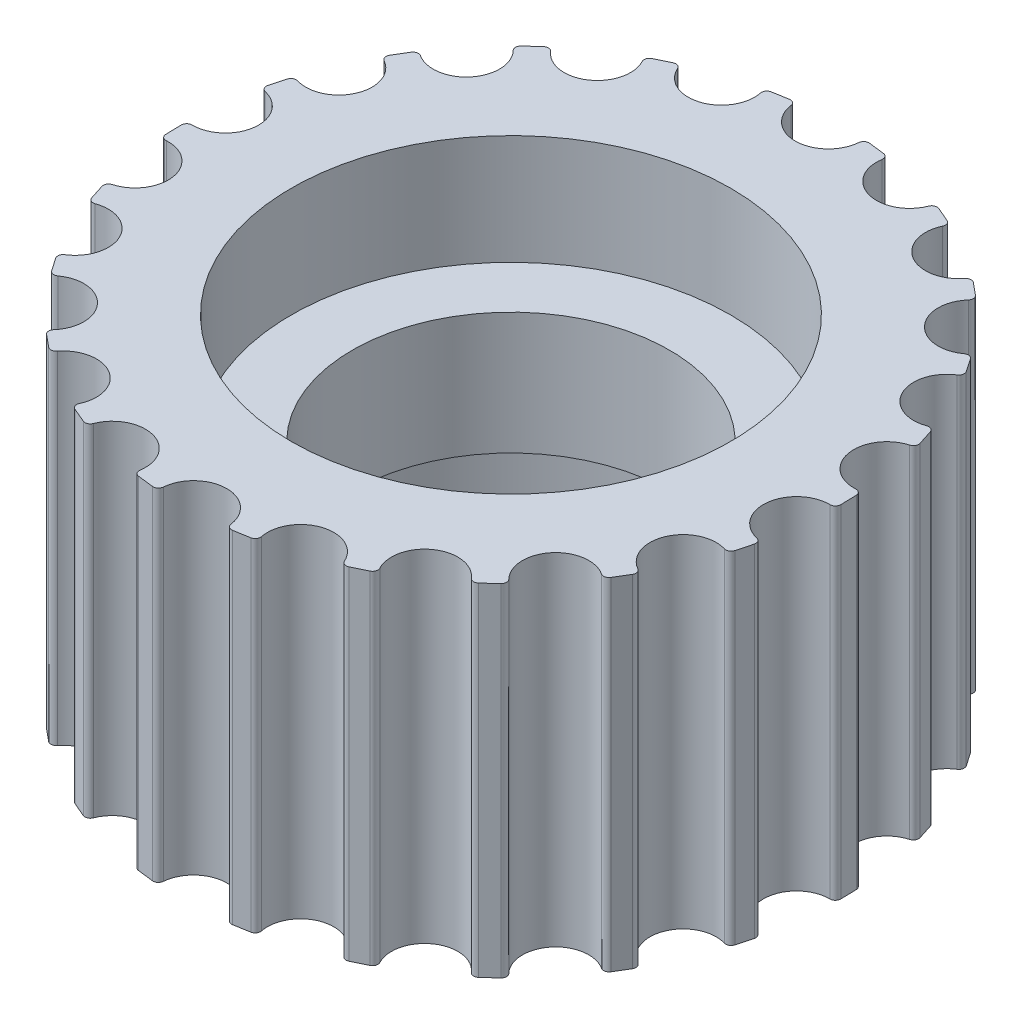
SolidWorks part; units mm, degrees
ref_plane "Front Plane" through (0, 0, 0) normal (0, 0, 1) x (1, 0, 0)
ref_plane "Top Plane" through (0, 0, 0) normal (0, 1, 0) x (1, 0, 0)
ref_plane "Right Plane" through (0, 0, 0) normal (1, 0, 0) x (0, 0, -1)
sketch "Sketch2" plane through (0, 0, 0) normal (0, 1, 0) x (1, 0, 0)
  line L0 (-1.2929, 6.625) -> (-0.973, 6.6795)
  line L1 (0.6256, 6.7209) -> (0.9479, 6.6831)
  line L2 (2.4934, 6.2725) -> (2.792, 6.1454)
  line L3 (4.1593, 5.3159) -> (4.4099, 5.1099)
  line L4 (5.4881, 3.9288) -> (5.6706, 3.6605)
  line L5 (6.3724, 2.2235) -> (6.4718, 1.9146)
  line L6 (6.7404, 0.3382) -> (6.7488, 0.0138)
  line L7 (6.5623, -1.5745) -> (6.479, -1.8881)
  line L8 (5.8526, -3.3595) -> (5.6843, -3.6369)
  line L9 (4.6687, -4.8722) -> (4.429, -5.091)
  line L10 (3.1066, -5.9901) -> (2.815, -6.1325)
  line L11 (1.2928, -6.6227) -> (0.9729, -6.6772)
  line L12 (-0.6257, -6.7186) -> (-0.948, -6.6808)
  line L13 (-2.4936, -6.2702) -> (-2.7921, -6.143)
  line L14 (-4.1594, -5.3136) -> (-4.4101, -5.1075)
  line L15 (-5.4883, -3.9265) -> (-5.6707, -3.6582)
  line L16 (-6.3725, -2.2212) -> (-6.472, -1.9123)
  line L17 (-6.7405, -0.3359) -> (-6.7489, -0.0115)
  line L18 (-6.5624, 1.5768) -> (-6.4791, 1.8904)
  line L19 (-5.8527, 3.3618) -> (-5.6844, 3.6392)
  line L20 (-4.6688, 4.8745) -> (-4.4292, 5.0933)
  line L21 (-3.1067, 5.9925) -> (-2.8151, 6.1349)
  circle A0 centre (0, 0) radius 4.5
  circle A1 centre (0, 0) radius 6 construction
  circle A2 centre (0, 0) radius 6.75 construction
  circle A3 centre (0, 0) radius 7.03 construction
  arc A4 (-0.973, 6.6795) -> (-0.8456, 6.5859) centre (-0.9546, 6.5711) cw
  arc A5 (-0.8456, 6.5859) -> (0.5058, 6.6207) centre (-0.1718, 6.6778) ccw
  arc A6 (0.5058, 6.6207) -> (0.6256, 6.7209) centre (0.6154, 6.6114) cw
  arc A7 (0.9479, 6.6831) -> (1.0438, 6.5574) centre (0.9351, 6.5738) cw
  arc A8 (1.0438, 6.5574) -> (2.3502, 6.21) centre (1.7162, 6.4557) ccw
  arc A9 (2.3502, 6.21) -> (2.4934, 6.2725) centre (2.4528, 6.1703) cw
  arc A10 (2.792, 6.1454) -> (2.8487, 5.9977) centre (2.7489, 6.0442) cw
  arc A11 (2.8487, 5.9977) -> (4.0043, 5.2964) centre (3.4651, 5.7107) ccw
  arc A12 (4.0043, 5.2964) -> (4.1593, 5.3159) centre (4.0915, 5.2293) cw
  arc A13 (4.4099, 5.1099) -> (4.4227, 4.9523) centre (4.3401, 5.0249) cw
  arc A14 (4.4227, 4.9523) -> (5.3339, 3.9537) centre (4.9333, 4.5032) ccw
  arc A15 (5.3339, 3.9537) -> (5.4881, 3.9288) centre (5.3987, 3.8648) cw
  arc A16 (5.6706, 3.6605) -> (5.6384, 3.5057) centre (5.5796, 3.5986) cw
  arc A17 (5.6384, 3.5057) -> (6.2314, 2.2909) centre (6.0019, 2.9309) ccw
  arc A18 (6.2314, 2.2909) -> (6.3724, 2.2235) centre (6.2685, 2.1873) cw
  arc A19 (6.4718, 1.9146) -> (6.3974, 1.7752) centre (6.3671, 1.8809) cw
  arc A20 (6.3974, 1.7752) -> (6.6241, 0.4425) centre (6.5842, 1.1213) ccw
  arc A21 (6.6241, 0.4425) -> (6.7404, 0.3382) centre (6.6305, 0.3327) cw
  arc A22 (6.7488, 0.0138) -> (6.638, -0.0991) centre (6.6388, 0.0109) cw
  arc A23 (6.638, -0.0991) -> (6.4801, -1.4416) centre (6.6331, -0.779) ccw
  arc A24 (6.4801, -1.4416) -> (6.5623, -1.5745) centre (6.4553, -1.5488) cw
  arc A25 (6.479, -1.8881) -> (6.3409, -1.9652) centre (6.3726, -1.8598) cw
  arc A26 (6.3409, -1.9652) -> (5.8111, -3.2088) centre (6.1446, -2.6162) ccw
  arc A27 (5.8111, -3.2088) -> (5.8526, -3.3595) centre (5.7572, -3.3047) cw
  arc A28 (5.6843, -3.6369) -> (5.5301, -3.672) centre (5.5902, -3.5799) cw
  arc A29 (5.5301, -3.672) -> (4.6714, -4.716) centre (5.1583, -4.2413) ccw
  arc A30 (4.6714, -4.716) -> (4.6687, -4.8722) centre (4.5926, -4.7928) cw
  arc A31 (4.429, -5.091) -> (4.2712, -5.0812) centre (4.3549, -5.0098) cw
  arc A32 (4.2712, -5.0812) -> (3.1532, -5.841) centre (3.7541, -5.5227) ccw
  arc A33 (3.1532, -5.841) -> (3.1066, -5.9901) centre (3.056, -5.8925) cw
  arc A34 (2.815, -6.1325) -> (2.6663, -6.0787) centre (2.7667, -6.0337) cw
  arc A35 (2.6663, -6.0787) -> (1.3795, -6.4927) centre (2.0457, -6.3566) ccw
  arc A36 (1.3795, -6.4927) -> (1.2928, -6.6227) centre (1.2717, -6.5147) cw
  arc A37 (0.9729, -6.6772) -> (0.8454, -6.5836) centre (0.9544, -6.5687) cw
  arc A38 (0.8454, -6.5836) -> (-0.5059, -6.6183) centre (0.1717, -6.6755) ccw
  arc A39 (-0.5059, -6.6183) -> (-0.6257, -6.7186) centre (-0.6155, -6.6091) cw
  arc A40 (-0.948, -6.6808) -> (-1.0439, -6.5551) centre (-0.9352, -6.5715) cw
  arc A41 (-1.0439, -6.5551) -> (-2.3504, -6.2077) centre (-1.7163, -6.4534) ccw
  arc A42 (-2.3504, -6.2077) -> (-2.4936, -6.2702) centre (-2.4529, -6.1679) cw
  arc A43 (-2.7921, -6.143) -> (-2.8488, -5.9954) centre (-2.749, -6.0418) cw
  arc A44 (-2.8488, -5.9954) -> (-4.0044, -5.294) centre (-3.4652, -5.7084) ccw
  arc A45 (-4.0044, -5.294) -> (-4.1594, -5.3136) centre (-4.0916, -5.227) cw
  arc A46 (-4.4101, -5.1075) -> (-4.4228, -4.9499) centre (-4.3402, -5.0226) cw
  arc A47 (-4.4228, -4.9499) -> (-5.334, -3.9514) centre (-4.9335, -4.5009) ccw
  arc A48 (-5.334, -3.9514) -> (-5.4883, -3.9265) centre (-5.3988, -3.8625) cw
  arc A49 (-5.6707, -3.6582) -> (-5.6385, -3.5033) centre (-5.5797, -3.5963) cw
  arc A50 (-5.6385, -3.5033) -> (-6.2315, -2.2885) centre (-6.002, -2.9286) ccw
  arc A51 (-6.2315, -2.2885) -> (-6.3725, -2.2212) centre (-6.2686, -2.185) cw
  arc A52 (-6.472, -1.9123) -> (-6.3975, -1.7728) centre (-6.3673, -1.8786) cw
  arc A53 (-6.3975, -1.7728) -> (-6.6242, -0.4402) centre (-6.5843, -1.119) ccw
  arc A54 (-6.6242, -0.4402) -> (-6.7405, -0.3359) centre (-6.6306, -0.3304) cw
  arc A55 (-6.7489, -0.0115) -> (-6.6381, 0.1014) centre (-6.6389, -0.0086) cw
  arc A56 (-6.6381, 0.1014) -> (-6.4802, 1.4439) centre (-6.6332, 0.7814) ccw
  arc A57 (-6.4802, 1.4439) -> (-6.5624, 1.5768) centre (-6.4554, 1.5511) cw
  arc A58 (-6.4791, 1.8904) -> (-6.341, 1.9675) centre (-6.3728, 1.8622) cw
  arc A59 (-6.341, 1.9675) -> (-5.8112, 3.2111) centre (-6.1447, 2.6185) ccw
  arc A60 (-5.8112, 3.2111) -> (-5.8527, 3.3618) centre (-5.7573, 3.307) cw
  arc A61 (-5.6844, 3.6392) -> (-5.5302, 3.6743) centre (-5.5903, 3.5822) cw
  arc A62 (-5.5302, 3.6743) -> (-4.6715, 4.7183) centre (-5.1584, 4.2436) ccw
  arc A63 (-4.6715, 4.7183) -> (-4.6688, 4.8745) centre (-4.5927, 4.7951) cw
  arc A64 (-4.4292, 5.0933) -> (-4.2713, 5.0835) centre (-4.355, 5.0121) cw
  arc A65 (-4.2713, 5.0835) -> (-3.1533, 5.8433) centre (-3.7542, 5.5251) ccw
  arc A66 (-3.1533, 5.8433) -> (-3.1067, 5.9925) centre (-3.0561, 5.8948) cw
  arc A67 (-2.8151, 6.1349) -> (-2.6665, 6.081) centre (-2.7668, 6.036) cw
  arc A68 (-2.6665, 6.081) -> (-1.3796, 6.495) centre (-2.0459, 6.359) ccw
  arc A69 (-1.3796, 6.495) -> (-1.2929, 6.625) centre (-1.2718, 6.5171) cw
  circle A70 centre (0, 0) radius 3.25
  point P185 (-0.0001, 0.0012)
  dimension "D1" = 9
  dimension "D2" = 12
  dimension "D3" = 13.5
  dimension "D4" = 14.06
  dimension "D5" = 0.11
  dimension "D6" = 0.68
  dimension "D7" = 0.11
  dimension "D8" = 22
  dimension "D9" = 6.5
extrude "Boss-Extrude1" add sketch "Sketch2" along normal mid plane 7 contours A69 A68 A67 L21 A66 A65 A64 L20 A63 A62 A61 L19 A60 A59 A58 L18 A57 A56 A55 L17 A54 A53 A52 L16 A51 A50 A49 L15 A48 A47 A46 L14 A45 A44 A43 L13 A42 A41 A40 L12 A39 A38 A37 L11 A36 A35 A34 L10 A33 A32 A31 region at (-1.101, 0, -6.4645)
extrude "Boss-Extrude2" add sketch "Sketch2<3>" along normal mid plane 2.5 contours A0 A70 region at (-4.3727, 0, 0)
sketch "Sketch2<3>" plane through (0, 0, 0) normal (0, 1, 0) x (1, 0, 0) same geometry as "Sketch2"
